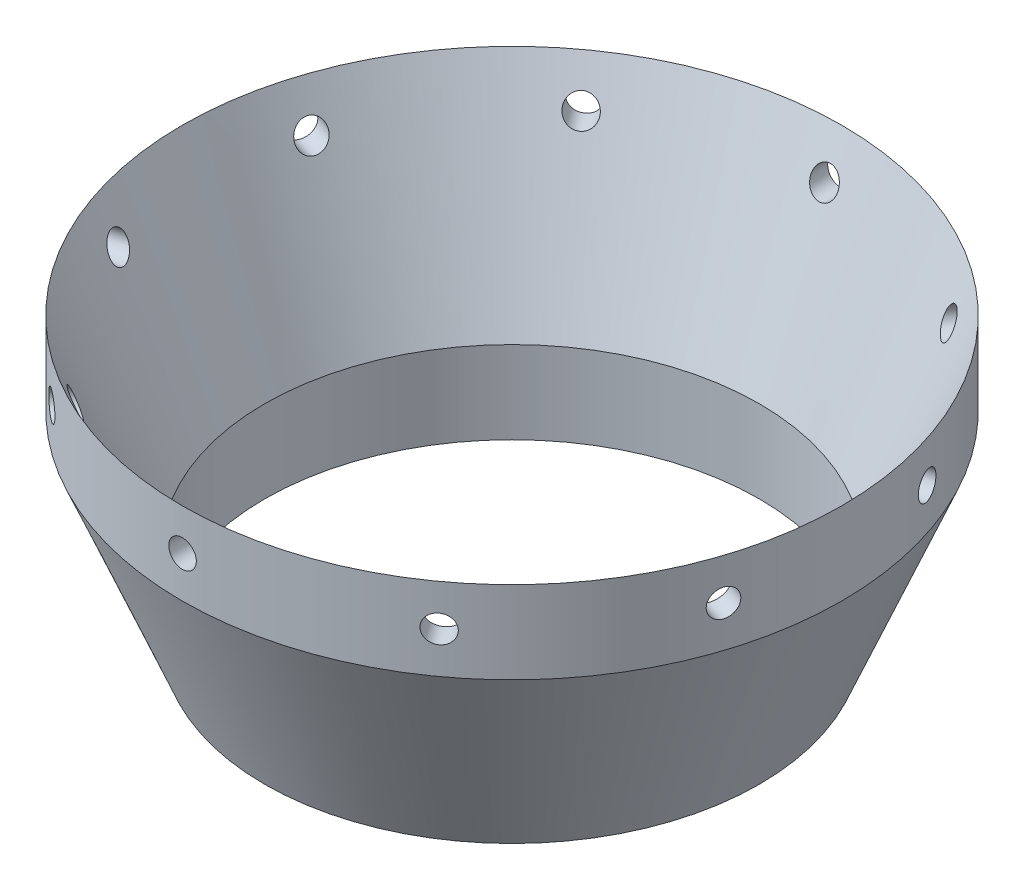
SolidWorks part; units mm, degrees
material "2024-T3"
ref_plane "Front Plane" through (0, 0, 0) normal (0, 0, 1) x (1, 0, 0)
ref_plane "Top Plane" through (0, 0, 0) normal (0, 1, 0) x (1, 0, 0)
ref_plane "Right Plane" through (0, 0, 0) normal (1, 0, 0) x (0, 0, -1)
sketch "Sketch1" plane through (0, 0, 0) normal (0, 0, 1) x (1, 0, 0)
  line L0 (0, 0) -> (0, 220.7687) construction
  line L1 (-57.15, 178.478) -> (-57.15, 197.528)
  line L2 (-57.15, 197.528) -> (-76.2, 243.756)
  line L3 (-76.2, 243.756) -> (-76.2, 224.706)
  line L4 (-76.2, 224.706) -> (-57.15, 178.478)
  dimension "D1" = 57.15
  dimension "D2" = 76.2
  dimension "D3" = 46.228
  dimension "D4" = 19.05
  dimension "D5" = 19.05
revolve "Revolve1" add sketch "Sketch1" angle 360 about L0
sketch "Sketch2" plane through (0, 0, 0) normal (0, 0, 1) x (1, 0, 0)
  line L0 (0, 235.8035) -> (0, 187.481) construction
  line L1 (76.2, 224.706) -> (-76.2, 224.706) construction
  circle A0 centre (0, 234.231) radius 3.175
  dimension "D1" = 9.525
extrude "Cut-Extrude1" cut sketch "Sketch2" against normal through all
ref_axis "Axis1" through (0, 235.8035, 0) along (0, -1, 0)
pattern_circular "CirPattern1" count 10 over 360 about axis through (0, 235.8035, 0) along (0, -1, 0) of "Cut-Extrude1"
